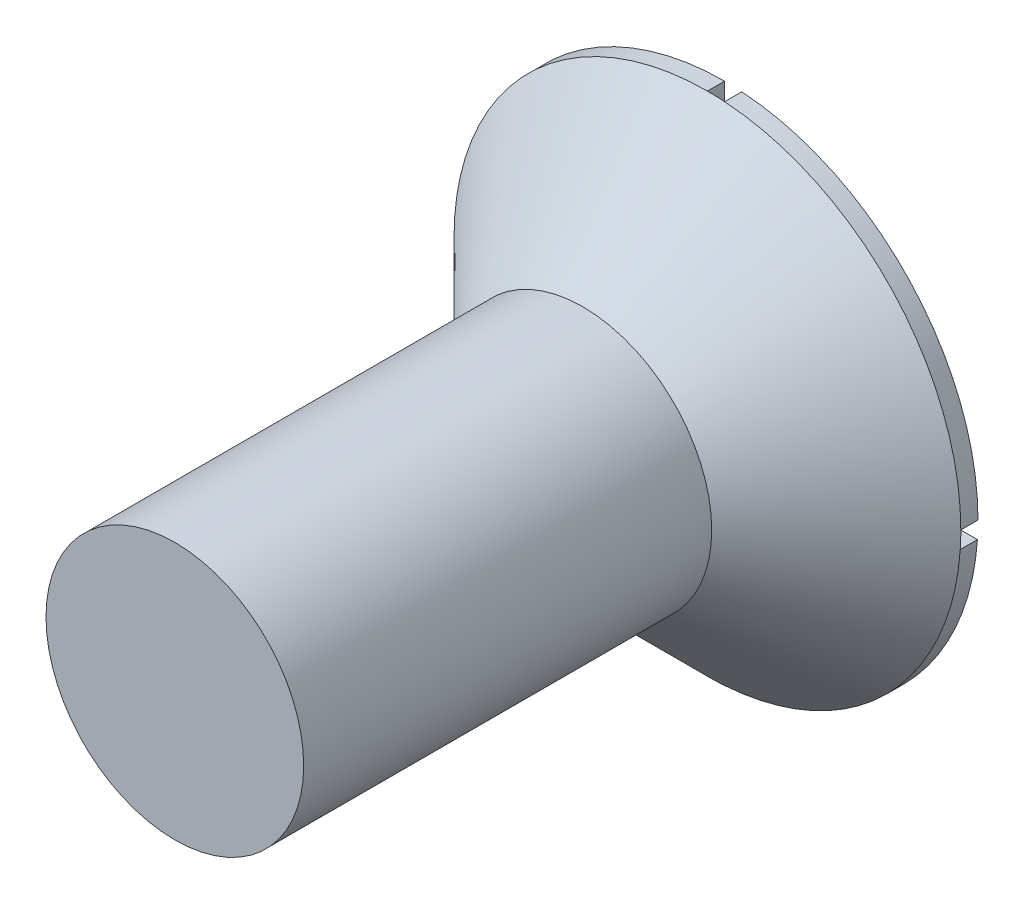
SolidWorks part; units mm, degrees
material "AISI 1020"
ref_plane "Plan de face" through (0, 0, 0) normal (0, 0, 1) x (1, 0, 0)
ref_plane "Plan de dessus" through (0, 0, 0) normal (0, 1, 0) x (1, 0, 0)
ref_plane "Plan de droite" through (0, 0, 0) normal (1, 0, 0) x (0, 0, -1)
sketch "Esquisse1" plane through (0, 0, 0) normal (0, 0, 1) x (1, 0, 0)
  circle A0 centre (0, 0) radius 1.5
  dimension "D1" = 3
extrude "Boss.-Extru.1" add sketch "Esquisse1" along normal blind 4
sketch "Esquisse2" plane through (0, 0, 0) normal (0, 0, -1) x (-1, 0, 0)
  circle A0 centre (0, 0) radius 2.95
  dimension "D1" = 5.9
extrude "Boss.-Extru.2" add sketch "Esquisse2" along normal blind 2.4
chamfer "Chanfrein1" distance 2.2 angle 45 1 edges at (-2.95, 0, 0)
sketch "Esquisse4" plane through (0, 0, -2.4) normal (0, 0, -1) x (-1, 0, 0)
  line L0 (0, 2.95) -> (0, -2.95)
  line L1 (-2.95, 0) -> (2.95, 0)
  circle A0 centre (0, 0) radius 2.95 construction
extrude "Enlèv. de mat.-Extru.-Mince1" cut sketch "Esquisse4" against normal blind 0.2 thin thin type one direction wall 0.2
